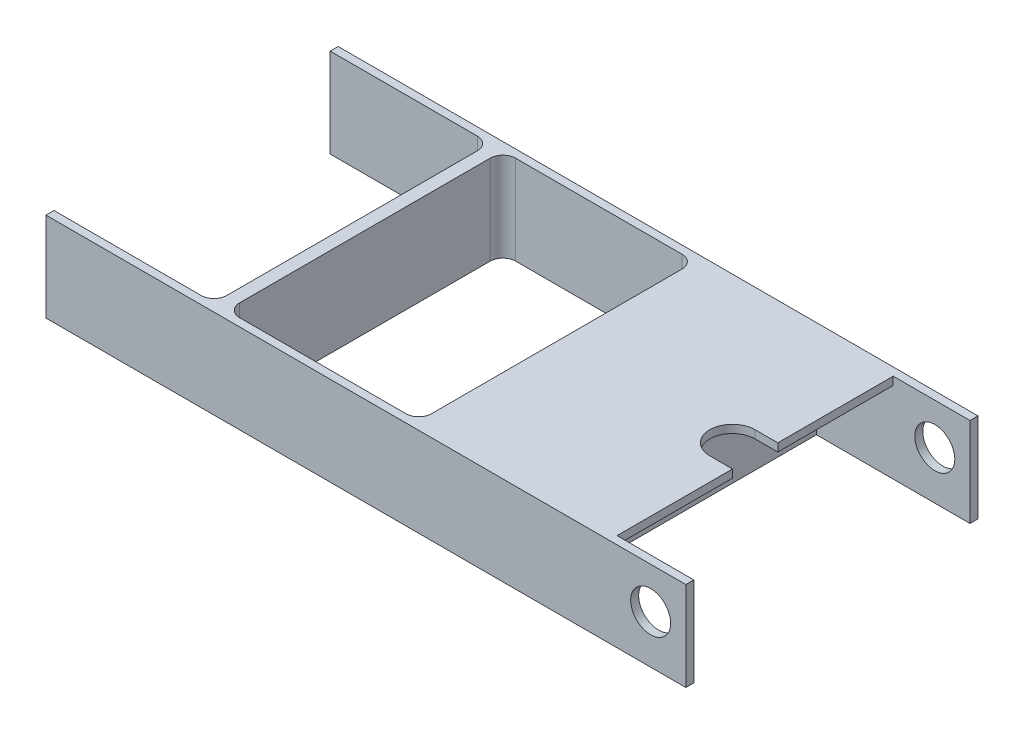
SolidWorks part; units mm, degrees
material "5052-H32"
ref_plane "Front Plane" through (0, 0, 0) normal (0, 0, 1) x (1, 0, 0)
ref_plane "Top Plane" through (0, 0, 0) normal (0, 1, 0) x (1, 0, 0)
ref_plane "Right Plane" through (0, 0, 0) normal (1, 0, 0) x (0, 0, -1)
sketch "Sketch1" plane through (0, 0, 0) normal (0, 1, 0) x (1, 0, 0)
  line L1 (63.5, 28.9941) -> (-63.5, 28.9941)
  line L2 (63.5, 28.9941) -> (63.5, -28.9941)
  line L3 (63.5, -28.9941) -> (-63.5, -28.9941)
  line L4 (-63.5, 28.9941) -> (-63.5, -28.9941)
  line L5 (63.5, 28.9941) -> (-63.5, -28.9941) construction
  line L6 (63.5, -28.9941) -> (-63.5, 28.9941) construction
  point P0 (0, 0)
  dimension "D1" = 127
  dimension "D2" = 57.9882
extrude "Boss-Extrude1" add sketch "Sketch1" along normal blind 17.7013
sketch "Sketch2" plane through (0, 17.7013, 0) normal (0, 1, 0) x (1, 0, 0)
  line L0 (48.26, 28.9941) -> (48.26, -28.9941)
  line L1 (63.5, 28.9941) -> (-63.5, 28.9941) construction
  line L2 (-63.5, -28.9941) -> (63.5, -28.9941) construction
  line L3 (-63.5, 28.9941) -> (-63.5, -28.9941) construction
  line L4 (48.26, 27.4066) -> (63.5, 27.4066)
  line L5 (63.5, -28.9941) -> (63.5, 28.9941) construction
  line L6 (48.26, -27.4066) -> (63.5, -27.4066)
  line M6 (63.5, -28.9941) -> (63.5, 28.9941)
  dimension "D1" = 111.76
  dimension "D2" = 1.5875
  dimension "D3" = 1.5875
extrude "Cut-Extrude1" cut sketch "Sketch2" against normal through all contours L0 L6 L4 M6 region at (55.88, 17.7013, 0)
sketch "Sketch3" plane through (0, 0, -27.4066) normal (0, 0, 1) x (1, 0, 0)
  line L0 (63.5, 0) -> (63.5, 17.7013) construction
  line L1 (48.26, 17.7013) -> (63.5, 17.7013) construction
  circle A0 centre (56.515, 9.5479) radius 3.9687
  dimension "D1" = 7.9375
  dimension "D2" = 6.985
  dimension "D3" = 8.1534
extrude "Cut-Extrude2" cut sketch "Sketch3" against normal through all both and the other way through all
sketch "Sketch4" plane through (0, 17.7013, 0) normal (0, 1, 0) x (1, 0, 0)
  line L0 (48.26, 27.4066) -> (48.26, -27.4066) construction
  line L1 (0, 0) -> (50000, 0) construction
  line L3 (43.76, 4.5) -> (48.26, 4.5)
  line L4 (43.76, -4.5) -> (48.26, -4.5)
  circle A0 centre (43.76, 0) radius 4.5
  line M10 (48.26, -27.4066) -> (48.26, 27.4066)
  dimension "D1" = 9
sketch "Sketch6" plane through (48.26, 0, 0) normal (1, 0, 0) x (0, 0, -1)
  line L0 (-27.4066, 16.1138) -> (27.4066, 16.1138)
  line L1 (-27.4066, 0) -> (-27.4066, 17.7013) construction
  line L2 (27.4066, 0) -> (27.4066, 17.7013) construction
  line L3 (27.4066, 17.7013) -> (-27.4066, 17.7013) construction
  line M3 (-27.4066, 17.7013) -> (-27.4066, 0)
  line M4 (-27.4066, 0) -> (27.4066, 0)
  line M5 (27.4066, 0) -> (27.4066, 17.7013)
  dimension "D1" = 1.5875
extrude "Cut-Extrude5" cut sketch "Sketch6" against normal blind 15.24 and the other way through all contours L0 M3 M4 M5 region at (48.26, 8.0569, 0)
extrude "Cut-Extrude6" cut sketch "Sketch4" against normal through all contours A0 L1 | A0 L3 M10 | L1 A0 | A0 L4 M10 region at (43.76, 17.7013, -1.9099) region at (43.76, 17.7013, 1.9099) region at (47.2548, 17.7013, 3.4948) region at (47.2548, 17.7013, -3.4948)
sketch "Sketch7" plane through (0, 17.7013, 0) normal (0, 1, 0) x (1, 0, 0)
  line L0 (48.26, 27.4066) -> (-63.5, 27.4066)
  line L1 (-63.5, 28.9941) -> (-63.5, -28.9941) construction
  line L2 (48.26, -27.4066) -> (-63.5, -27.4066)
  line L3 (-31.75, 27.4066) -> (-31.75, -27.4066)
  line M8 (-63.5, 28.9941) -> (-63.5, -28.9941)
  dimension "D1" = 31.75
extrude "Cut-Extrude7" cut sketch "Sketch7" against normal through all contours L3 L0 L2 M8 region at (-47.625, 17.7013, 0)
sketch "Sketch8" plane through (0, 17.7013, 0) normal (0, 1, 0) x (1, 0, 0)
  line L0 (-31.75, 27.4066) -> (48.26, 27.4066)
  line L1 (-31.75, -27.4066) -> (48.26, -27.4066)
  line L2 (-29.21, 27.4066) -> (-29.21, -27.4066)
  line L3 (8.89, 27.4066) -> (8.89, -27.4066)
  line L4 (-31.75, 27.4066) -> (-31.75, -27.4066) construction
  dimension "D1" = 2.54
  dimension "D2" = 38.1
extrude "Cut-Extrude8" cut sketch "Sketch8" against normal through all contours L3 L0 L2 L1 region at (-10.16, 17.7013, 0)
fillet "Fillet2" radius 2.54 6 edges at (-29.21, 8.8506, 27.4066) (-31.75, 8.8506, 27.4066) (8.89, 8.8506, 27.4066) (8.89, 8.8506, -27.4066) (-29.21, 8.8506, -27.4066) (-31.75, 8.8506, -27.4066)
